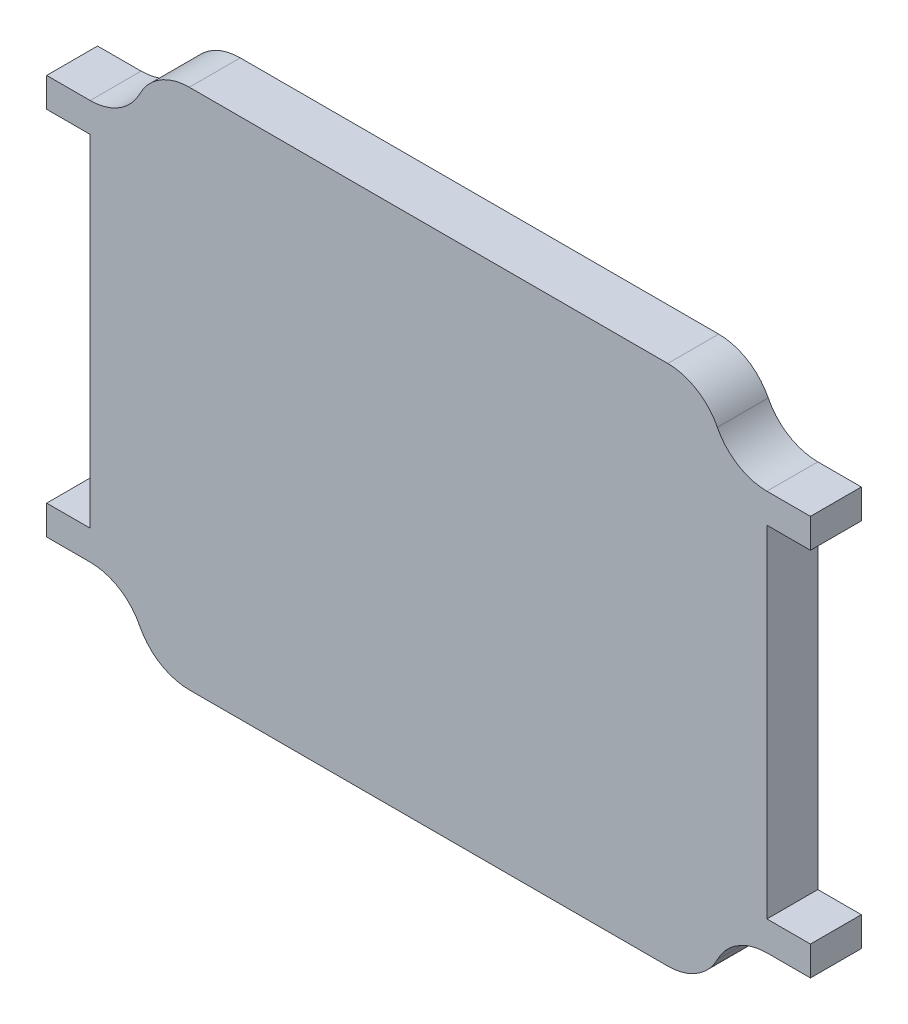
SolidWorks part; units mm, degrees
material "Acrylic (Medium-high impact)"
ref_plane "Front Plane" through (0, 0, 0) normal (0, 0, 1) x (1, 0, 0)
ref_plane "Top Plane" through (0, 0, 0) normal (0, 1, 0) x (1, 0, 0)
ref_plane "Right Plane" through (0, 0, 0) normal (1, 0, 0) x (0, 0, -1)
sketch "Sketch1" plane through (0, 0, 0) normal (0, 0, 1) x (1, 0, 0)
  line L0 (-1000, 0) -> (49000, 0) construction
  line L2 (-38.9, 19.6) -> (-38.9, -19.6)
  line L3 (-38.9, 19.6) -> (-43.9, 19.6)
  line L4 (-43.9, 19.6) -> (-43.9, 22.98)
  line L5 (-43.9, 22.98) -> (-38.9, 22.98)
  line L6 (-43.9, -22.98) -> (-38.9, -22.98)
  line L7 (-43.9, -19.6) -> (-43.9, -22.98)
  line L8 (-38.9, -19.6) -> (-43.9, -19.6)
  line L9 (-27.5, 30) -> (27.5, 30)
  line L10 (-38.9, 29.3632) -> (-27.5, 23.6168) construction
  line L11 (-27.5, -30) -> (27.5, -30)
  line L12 (43.9, -22.98) -> (38.9, -22.98)
  line L13 (43.9, -19.6) -> (43.9, -22.98)
  line L14 (38.9, -19.6) -> (43.9, -19.6)
  line L15 (38.9, 19.6) -> (38.9, -19.6)
  line L16 (38.9, 19.6) -> (43.9, 19.6)
  line L17 (43.9, 19.6) -> (43.9, 22.98)
  line L18 (43.9, 22.98) -> (38.9, 22.98)
  arc A0 (-38.9, 22.98) -> (-33.2, 26.49) centre (-38.9, 29.3632) ccw
  arc A1 (-33.2, 26.49) -> (-27.5, 30) centre (-27.5, 23.6168) cw
  arc A2 (-33.2, -26.49) -> (-27.5, -30) centre (-27.5, -23.6168) ccw
  arc A3 (-38.9, -22.98) -> (-33.2, -26.49) centre (-38.9, -29.3632) cw
  arc A4 (33.2, -26.49) -> (27.5, -30) centre (27.5, -23.6168) cw
  arc A5 (38.9, -22.98) -> (33.2, -26.49) centre (38.9, -29.3632) ccw
  arc A6 (38.9, 22.98) -> (33.2, 26.49) centre (38.9, 29.3632) cw
  arc A7 (33.2, 26.49) -> (27.5, 30) centre (27.5, 23.6168) ccw
  point P4 (-38.9, 0)
  point P16 (0, 30)
  point P17 (-33.2, 26.49)
  dimension "D5" = 6.3832
  dimension "D1" = 30
  dimension "D2" = 39.2
  dimension "D3" = 3.38
  dimension "D4" = 5
  dimension "D6" = 55
extrude "Boss-Extrude1" add sketch "Sketch1" along normal blind 5.85
